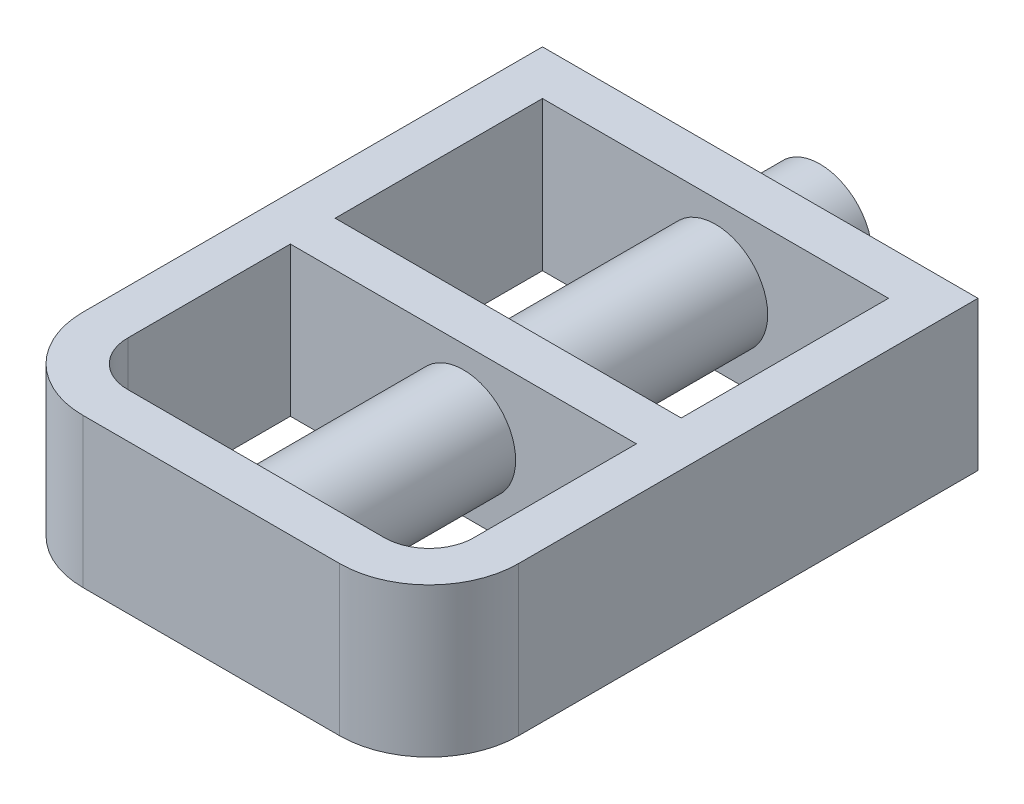
SolidWorks part; units mm, degrees
ref_plane "Alzado" through (0, 0, 0) normal (0, 0, 1) x (1, 0, 0)
ref_plane "Planta" through (0, 0, 0) normal (0, 1, 0) x (1, 0, 0)
ref_plane "Vista lateral" through (0, 0, 0) normal (1, 0, 0) x (0, 0, -1)
sketch "Croquis1" plane through (0, 0, 0) normal (0, 1, 0) x (1, 0, 0)
  line L0 (-29, -31) -> (-29, -3.75)
  line L1 (21.5, -46) -> (-21.5, -46)
  line L2 (36.5, -31) -> (36.5, 46)
  line L3 (36.5, 46) -> (-36.5, 46)
  line L4 (-36.5, -31) -> (-36.5, 46)
  line L5 (36.5, -46) -> (2.9755, -3.75) construction
  line L6 (36.5, 46) -> (0, 0) construction
  line L7 (29, 38.5) -> (-29, 38.5)
  line L8 (29, -31) -> (29, -3.75)
  line L9 (21.5, -38.5) -> (-21.5, -38.5)
  line L10 (-29, 3.75) -> (-29, 38.5)
  line L11 (29, -3.75) -> (-29, -3.75)
  line L13 (29, 3.75) -> (-29, 3.75)
  line L15 (0, 0) -> (-29, 3.75) construction
  line L16 (29, 3.75) -> (0, 0) construction
  line L17 (-29, -31) -> (-29, 38.5) construction
  line L18 (-2.9755, -3.75) -> (-36.5, -46) construction
  line L19 (0, 0) -> (-36.5, 46) construction
  line L20 (29, 3.75) -> (29, 38.5)
  line L21 (29, -31) -> (29, 38.5) construction
  arc A0 (21.5, -46) -> (36.5, -31) centre (21.5, -31) ccw
  arc A1 (-21.5, -46) -> (-36.5, -31) centre (-21.5, -31) cw
  arc A2 (21.5, -38.5) -> (29, -31) centre (21.5, -31) ccw
  arc A3 (-21.5, -38.5) -> (-29, -31) centre (-21.5, -31) cw
  point P0 (0, 0)
  point P20 (0, 0)
  dimension "D3" = 15
  dimension "D1" = 92
  dimension "D2" = 73
  dimension "D5" = 7.5
  dimension "D4" = 7.5
extrude "Saliente-Extruir1" add sketch "Croquis1" along normal mid plane 25
sketch "Croquis2" plane through (0, 0, -46) normal (0, 0, -1) x (-1, 0, 0)
  circle A0 centre (0, 0) radius 8.75
  dimension "D1" = 17.5
extrude "Saliente-Extruir2" add sketch "Croquis2" against normal up to surface (84.5 mm away) and the other way blind 10 up to face at (0, 0, 38.5)
sketch "Croquis3" plane through (0, 0, -56) normal (0, 0, -1) x (-1, 0, 0)
  circle A0 centre (0, 0) radius 5
  dimension "D1" = 10
extrude "Cortar-Extruir1" cut sketch "Croquis3" against normal up to surface (94.5 mm away) up to face at (-8.75, 0, 38.5)
